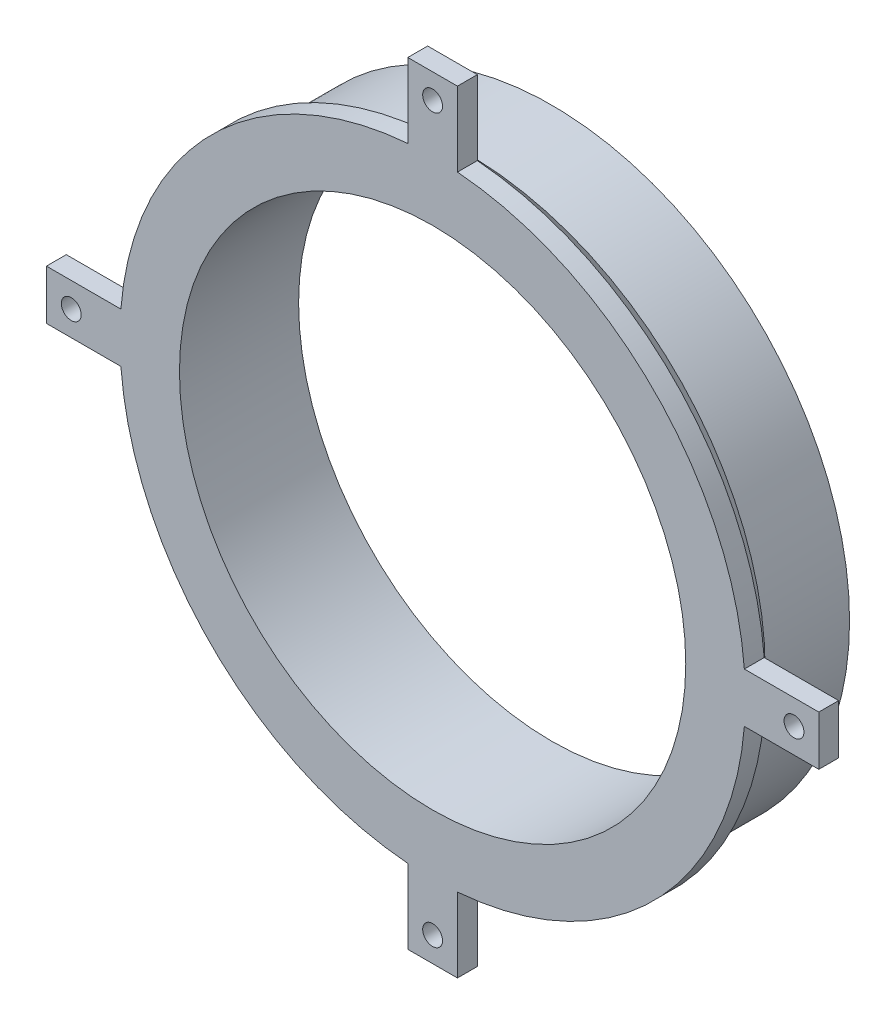
SolidWorks part; units mm, degrees
ref_plane "Front Plane" through (0, 0, 0) normal (0, 0, 1) x (1, 0, 0)
ref_plane "Top Plane" through (0, 0, 0) normal (0, 1, 0) x (1, 0, 0)
ref_plane "Right Plane" through (0, 0, 0) normal (1, 0, 0) x (0, 0, -1)
sketch "Sketch3" plane through (0, 0, 0) normal (0, 0, 1) x (1, 0, 0)
  circle A0 centre (0, 0) radius 55 construction
  circle A2 centre (0, 0) radius 57 construction
  circle A3 centre (0, 0) radius 51
  circle A4 centre (0, 0) radius 60
  dimension "D1" = 110
  dimension "D3" = 114
  dimension "D2" = 4
  dimension "D4" = 3
extrude "Boss-Extrude2" add sketch "Sketch3" along normal blind 4
sketch "Sketch4" plane through (0, 0, 4) normal (0, 0, 1) x (1, 0, 0)
  line L0 (0, 60) -> (0, 77.8013) construction
  line L3 (-5, 77.8013) -> (5, 77.8013)
  line L4 (5, 77.8013) -> (5, 62.8013)
  line L5 (-5, 77.8013) -> (-5, 62.8013)
  line L6 (77.8013, 5) -> (77.8013, -5)
  line L7 (77.8013, -5) -> (62.8013, -5)
  line L8 (77.8013, 5) -> (62.8013, 5)
  line L9 (60, 0) -> (77.8013, 0) construction
  line L10 (5, -77.8013) -> (-5, -77.8013)
  line L11 (-5, -77.8013) -> (-5, -62.8013)
  line L12 (5, -77.8013) -> (5, -62.8013)
  line L13 (0, -60) -> (0, -77.8013) construction
  line L14 (-77.8013, -5) -> (-77.8013, 5)
  line L15 (-77.8013, 5) -> (-62.8013, 5)
  line L16 (-77.8013, -5) -> (-62.8013, -5)
  line L17 (-60, 0) -> (-77.8013, 0) construction
  circle A0 centre (0, 72.8013) radius 2
  circle A2 centre (0, 0) radius 60
  arc A3 (-5, 62.8013) -> (-62.8013, 5) centre (0, 0) ccw
  circle A4 centre (72.8013, 0) radius 2
  circle A5 centre (0, -72.8013) radius 2
  circle A6 centre (-72.8013, 0) radius 2
  circle A7 centre (0, 0) radius 63 construction
  arc A8 (-62.8013, -5) -> (-5, -62.8013) centre (0, 0) ccw
  arc A9 (5, -62.8013) -> (62.8013, -5) centre (0, 0) ccw
  arc A10 (62.8013, 5) -> (5, 62.8013) centre (0, 0) ccw
  point P33 (0, 0)
  point P42 (0, 0)
  dimension "D5" = 4
  dimension "D4" = 120
  dimension "D1" = 3
  dimension "D2" = 15
  dimension "D3" = 5
  dimension "D6" = 4
  dimension "D7" = 5
extrude "Boss-Extrude3" add sketch "Sketch4" against normal blind 4
sketch "Sketch5" plane through (0, 0, 0) normal (0, 0, -1) x (-1, 0, 0)
  circle A2 centre (0, 0) radius 60
  circle A3 centre (0, 0) radius 57
extrude "Boss-Extrude4" add sketch "Sketch5" along normal blind 20
sketch "Sketch6" plane through (0, 0, 0) normal (0, 0, -1) x (-1, 0, 0)
  circle A0 centre (0, 0) radius 55
  circle A1 centre (0, 0) radius 51
extrude "Boss-Extrude5" add sketch "Sketch6" along normal blind 20
chamfer "Chamfer1" distance 3 angle 45 1 edges at (-60, 0, 0)
